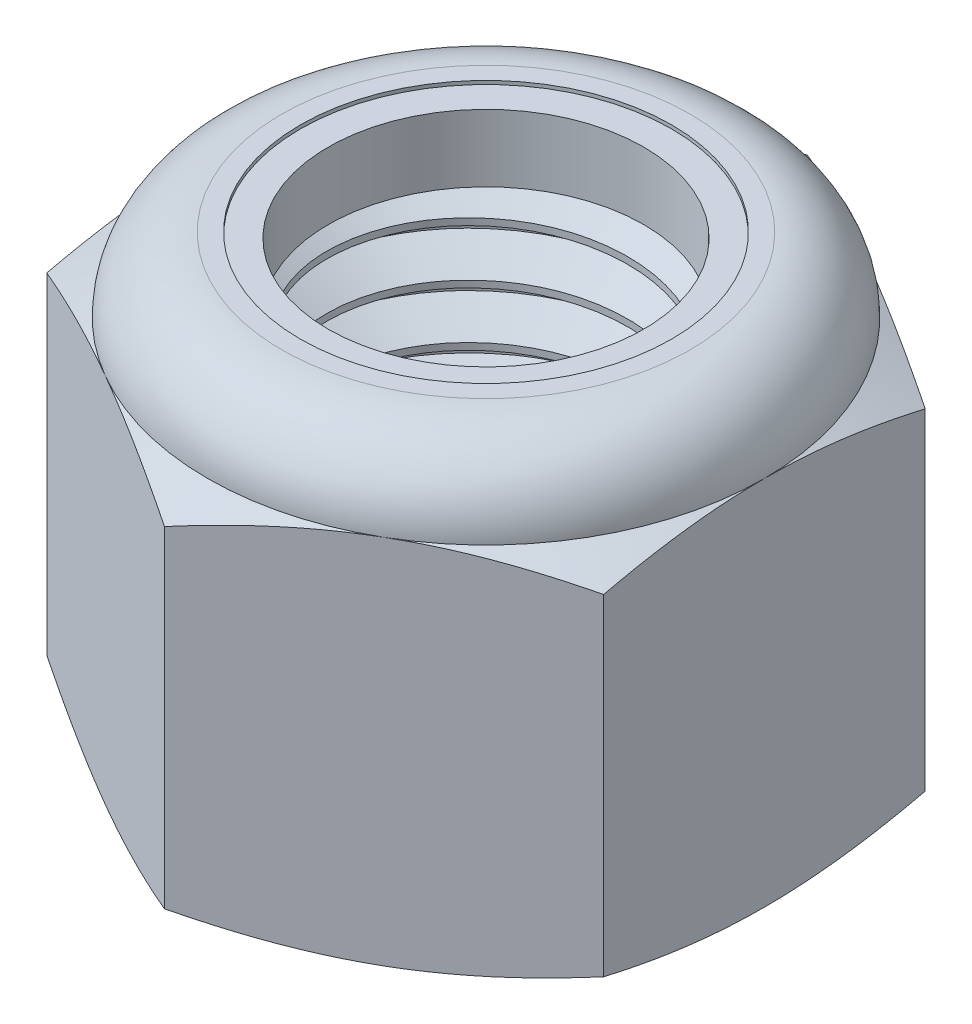
SolidWorks part; units mm, degrees
material "Plain Carbon Steel"
ref_plane "Front" through (0, 0, 0) normal (0, 0, 1) x (1, 0, 0)
ref_plane "Top" through (0, 0, 0) normal (0, 1, 0) x (1, 0, 0)
ref_plane "Right" through (0, 0, 0) normal (1, 0, 0) x (0, 0, -1)
sketch "Sketch1" plane through (0, 0, 0) normal (1, 0, 0) x (0, 0, -1)
  line L0 (0, 0) -> (0, 19.05) construction
  line L1 (11.9062, 0) -> (-11.9062, 0) construction
  line L2 (-7.9375, 19.05) -> (7.9375, 19.05) construction
  line L3 (7.9375, 19.05) -> (7.9375, 16.7409) construction
  point P9 (-7.9375, 19.05)
  point P10 (7.9375, 19.05)
  point P11 (11.9062, 0)
  dimension "Height" = 19.05
  dimension "Hex Flats" = 23.8125
  dimension "Thread Dia" = 15.875
  dimension "Thread Pitch" = 2.3091
sketch "Sketch13" plane through (0, 0, 0) normal (0, 1, 0) x (1, 0, 0)
  line L1 (0, 13.7482) -> (-11.9063, 6.8741)
  line L2 (-11.9063, 6.8741) -> (-11.9062, -6.8741)
  line L3 (-11.9062, -6.8741) -> (0, -13.7482)
  line L4 (0, -13.7482) -> (11.9063, -6.8741)
  line L5 (11.9063, -6.8741) -> (11.9063, 6.8741)
  line L6 (11.9063, 6.8741) -> (0, 13.7482)
  circle A0 centre (0, 0) radius 11.9062 construction
  circle A1 centre (0, 0) radius 7.9375
  point P11 (0, -7.9375)
  point P13 (0, 7.9375)
extrude "Extrude1" add sketch "Sketch13" along normal up to vertex (19.05 mm away) up to point (0, 19.05, 0)
sketch "Sketch5" plane through (0, 0, 0) normal (1, 0, 0) x (0, 0, -1)
  line L0 (0, 0) -> (11.9062, 0)
  line L1 (11.9062, 0) -> (13.7482, 0.8589)
  line L2 (13.7482, 0.8589) -> (13.7482, 15.0161)
  line L3 (13.7482, 15.0161) -> (11.9062, 15.875)
  line L4 (8.7312, 19.05) -> (8.7312, 20.32)
  line L5 (8.7312, 20.32) -> (15.0182, 20.32)
  line L6 (15.0182, 20.32) -> (15.0182, -1.27)
  line L7 (15.0182, -1.27) -> (0, -1.27)
  line L8 (0, -1.27) -> (0, 0)
  line L9 (11.9062, 15.875) -> (11.9062, 0) construction
  line L12 (13.7482, 19.05) -> (13.7482, 0) construction
  line L13 (13.7482, 9.525) -> (15.0182, 9.525) construction
  line L15 (0, 0) -> (0, 20.32) construction
  line L18 (11.9062, 0) -> (-11.9062, 0) construction
  line L19 (6.8741, 19.05) -> (13.7482, 19.05) construction
  line L20 (0, 20.32) -> (8.7312, 20.32) construction
  line L21 (6.8741, 0) -> (13.7482, 0) construction
  arc A0 (11.9062, 15.875) -> (8.7312, 19.05) centre (8.7312, 15.875) ccw
  dimension "D1" = 25
  dimension "D2" = 1.27
  dimension "D4" = 3.175
revolve "Cut-Revolve3" cut sketch "Sketch5" angle 360 about L15
sketch "Sketch4" plane through (0, 0, 0) normal (1, 0, 0) x (0, 0, -1)
  line L0 (0, 15.875) -> (8.7312, 15.875)
  line L1 (8.7312, 15.875) -> (0, 11.8036)
  line L3 (0, 4.0714) -> (8.7312, 0)
  line L4 (8.7312, 0) -> (0, 0)
  line L5 (0, 0) -> (0, 15.875) construction
  line L10 (0, 0) -> (0, 19.05) construction
  line L11 (0, 4.0714) -> (0, 0)
  line L12 (0, 15.875) -> (0, 11.8036)
  line L13 (10.3111, 15.875) -> (0, 15.875) construction
  dimension "D1" = 25
  dimension "D2" = 17.4625
sketch "Sketch6" plane through (0, 0, 0) normal (1, 0, 0) x (0, 0, -1)
  line L0 (0, 15.875) -> (11.7539, 15.875)
  line L1 (8.7312, 18.8976) -> (4.3656, 18.8976)
  line L2 (0, 20.32) -> (0, 15.875)
  line L3 (4.3656, 20.32) -> (0, 20.32)
  line L4 (0, 20.32) -> (8.7312, 20.32) construction
  line L5 (0, 0) -> (0, 20.32) construction
  line L6 (0, 20.32) -> (0, 0) construction
  line L7 (4.3656, 18.8976) -> (4.3656, 20.32)
  line L8 (8.7312, 19.05) -> (8.7312, 18.8976) construction
  line L9 (4.3656, 18.8976) -> (0, 18.8976) construction
  line L10 (0, 18.8976) -> (0, 11.8036) construction
  arc A0 (11.7539, 15.875) -> (8.7312, 18.8976) centre (8.7312, 15.875) ccw
  arc A1 (11.9062, 15.875) -> (8.7312, 19.05) centre (8.7312, 15.875) ccw construction
  dimension "D1" = 0.1524
revolve "Cut-Revolve4" cut sketch "Sketch6" angle 360 about L6
revolve "Cut-Revolve2" cut sketch "Sketch4" angle 360 about L5
sketch "Sketch7" plane through (0, 0, 0) normal (1, 0, 0) x (0, 0, -1)
  line L0 (6.7469, 15.9512) -> (11.6767, 15.9512)
  line L1 (8.7312, 18.8214) -> (6.7469, 18.8214)
  line L2 (6.7469, 18.8214) -> (6.7469, 15.9512)
  line L3 (6.7469, 15.9512) -> (0, 15.9512) construction
  line L4 (0, 15.9512) -> (0, 18.8214) construction
  line L5 (0, 18.8214) -> (6.7469, 18.8214) construction
  line L6 (6.7469, 15.9512) -> (6.7469, 15.875) construction
  line L7 (0, 15.875) -> (11.7539, 15.875) construction
  line L8 (8.7312, 18.8214) -> (8.7312, 18.8976) construction
  arc A0 (11.6767, 15.9512) -> (8.7312, 18.8214) centre (8.7312, 15.875) ccw
  arc A2 (11.7539, 15.875) -> (8.7312, 18.8976) centre (8.7312, 15.875) ccw construction
  point P15 (6.7469, 18.8214)
  point P18 (-7.7391, 18.8214)
  point P19 (7.7391, 18.8214)
  dimension "D1" = 0.0762
  dimension "D2" = 13.4937
revolve "Revolve2" add sketch "Sketch7" angle 360 about L4
sketch "Sketch2" plane through (0, 0, 0) normal (1, 0, 0) x (0, 0, -1)
  line L0 (-7.9375, 0) -> (-7.9375, 15.875) construction
  line L1 (0, 0) -> (7.9375, 0)
  line L2 (0, 0) -> (0, 15.875)
  line L3 (0, 15.875) -> (7.9375, 15.875)
  line L4 (7.9375, 0) -> (7.9375, 15.875)
  line L6 (10.3111, 15.875) -> (11.9062, 15.875) construction
  line L7 (0, -7.9375) -> (0, 0) construction
revolve "Revolve1" add sketch "Sketch2" angle 360 about L7
sketch "Sketch9" plane through (0, 0, 0) normal (1, 0, 0) x (0, 0, -1)
  line L0 (8.1875, 18.0398) -> (8.1875, 15.7307) construction
  line L1 (8.1875, 15.7307) -> (6.1877, 16.8852) construction
  line L2 (6.1877, 16.8852) -> (8.1875, 18.0398) construction
  line L3 (6.4377, 17.0295) -> (6.4377, 16.7409) construction
  line L4 (7.9375, 17.8955) -> (7.9375, 15.875) construction
  line L5 (6.1877, 16.8852) -> (6.4377, 16.8852) construction
  line L6 (7.9375, 16.8852) -> (8.1875, 16.8852) construction
  line L7 (8.0625, 16.8852) -> (8.0625, 17.9676) construction
  line L8 (8.1875, 15.7307) -> (8.0625, 17.9676)
  line L9 (8.0625, 17.9676) -> (6.4377, 17.0295)
  line L10 (6.4377, 17.0295) -> (6.4377, 16.7409)
  line L11 (6.4377, 16.7409) -> (8.1875, 15.7307)
  dimension "D1" = 2.3091
  dimension "D2" = 0.2886
sketch "Sketch10" plane through (0, 15.875, 0) normal (0, 1, 0) x (1, 0, 0)
  circle A1 centre (0, 0) radius 7.9375
  circle A2 centre (0, 0) radius 7.9375
  dimension "D1" = 0
curve "Helix/Spiral1" pitch 2.3091 height 21.3591 turns 9.25
sweep "Cut-Sweep1" cut profiles "Sketch9" path "Helix/Spiral1"
sketch "Sketch11" plane through (0, 0, 0) normal (1, 0, 0) x (0, 0, -1)
  line L0 (0, 0) -> (0, 19.05) construction
  line L1 (11.9062, 0) -> (-11.9062, 0) construction
  line L4 (0, 19.05) -> (0, 0) construction
  line L5 (0, 9.525) -> (7.9375, 9.525) construction
  line L6 (0, 0) -> (8.7313, 0)
  line L7 (0, 4.0714) -> (0, 0)
  line L8 (8.7313, 0) -> (0, 4.0714)
  dimension "D1" = 17.4625
  dimension "D2" = 25
revolve "Revolve3" add sketch "Sketch11" angle 360 about L4
sketch "Sketch12" plane through (0, 0, 0) normal (1, 0, 0) x (0, 0, -1)
  line L0 (8.7312, 15.875) -> (0, 15.875)
  line L1 (0, 15.875) -> (0, 0)
  line L2 (0, 0) -> (8.7312, 0)
  line L3 (11.9062, 0) -> (-11.9062, 0) construction
  line L4 (8.7312, 0) -> (8.7312, 15.875)
  line L5 (-8.7312, 0) -> (8.7312, 0) construction
revolve "Revolve4" add sketch "Sketch12" angle 360 about L0
combine bodies "Combine1" bodies to combine 136 133
equation "\"D4@Sketch5\" = \"Height@Sketch1\" / 6"
equation "\"D1@Sketch9\" = \"Thread Pitch@Sketch1\""
equation "\"D2@Sketch9\" = \"Thread Pitch@Sketch1\" / 8"
equation "\"D4@Helix/Spiral1\" = \"Thread Pitch@Sketch1\""
equation "\"D3@Helix/Spiral1\" = \"Thread Pitch@Sketch1\" + \"Height@Sketch1\""
equation "\"D2@Sketch4\" = \"Thread Dia@Sketch1\" * 1.1"
equation "\"D1@Sketch11\" = \"Thread Dia@Sketch1\" * 1.1"
equation "\"D2@Sketch7\" = \"Thread Dia@Sketch1\" * .85"
